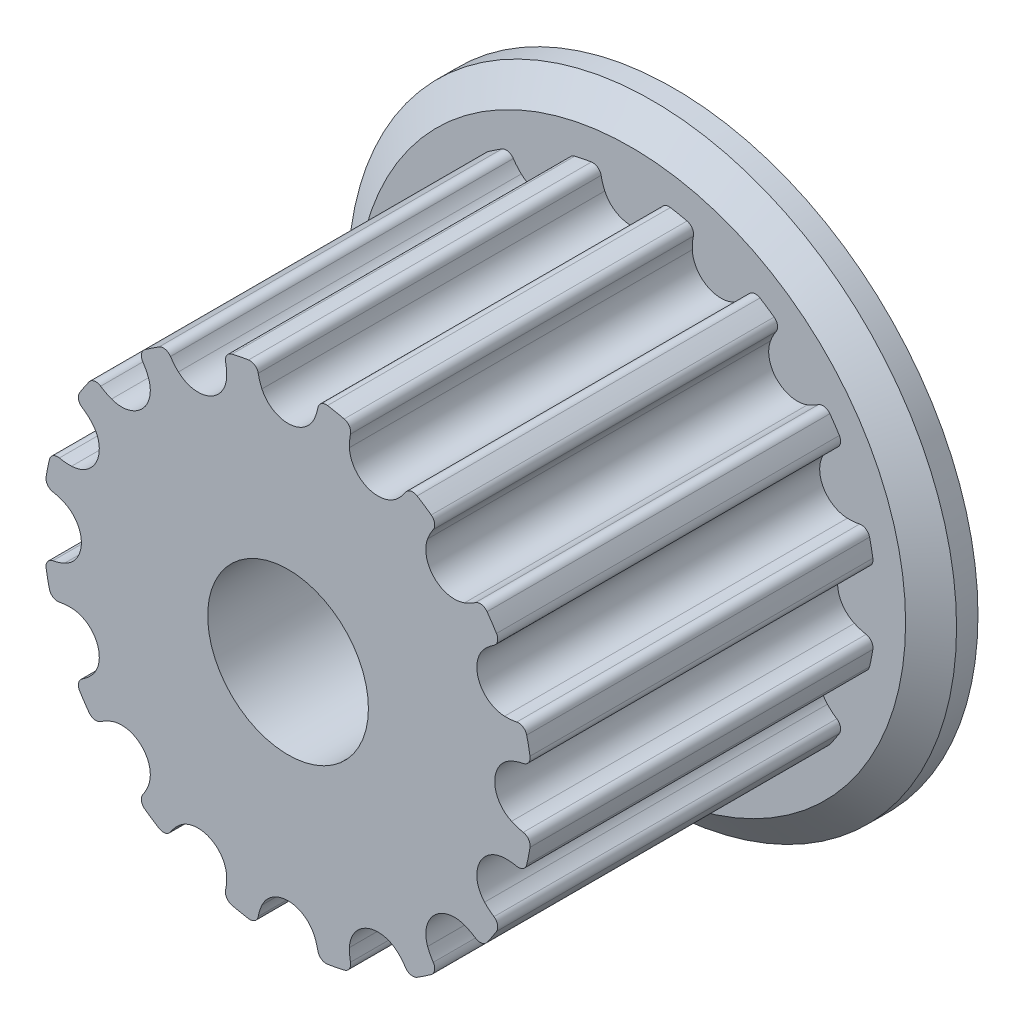
SolidWorks part; units mm, degrees
ref_plane "Front Plane" through (0, 0, 0) normal (0, 0, 1) x (1, 0, 0)
ref_plane "Top Plane" through (0, 0, 0) normal (0, 1, 0) x (1, 0, 0)
ref_plane "Right Plane" through (0, 0, 0) normal (1, 0, 0) x (0, 0, -1)
sketch "Sketch1" plane through (0, 0, 0) normal (0, 0, 1) x (1, 0, 0)
  line L1 (-2.553, 6.1245) -> (2.553, 6.1245) construction
  line L4 (0, 0) -> (0, 6.1245) construction
  line L5 (0, 6.1245) -> (0, 12.0714) construction
  line L6 (0, 7.6455) -> (2.9417, 7.0569) construction
  line L7 (2.9417, 7.0569) -> (3.8741, 6.6682) construction
  line L8 (2.9417, 7.0569) -> (2.553, 6.1245) construction
  line L9 (-2.9417, 7.0569) -> (-2.553, 6.1245) construction
  line L10 (-2.7951, 6.7052) -> (-3.7579, 9.015)
  line L11 (-3.7579, 9.015) -> (3.7579, 9.015)
  line L12 (3.7579, 9.015) -> (2.7951, 6.7052)
  circle A0 centre (0, 0) radius 7.6455 construction
  circle A1 centre (0, 0) radius 9.015 construction
  circle A2 centre (0, 0) radius 7.2645 construction
  arc A3 (-0.7739, 6.6229) -> (0.7739, 6.6229) centre (0, 6.9745) ccw
  arc A4 (-0.7739, 6.6229) -> (-0.8836, 6.9694) centre (0.61, 7.2516) cw
  arc A5 (-2.7951, 6.7052) -> (-1.1695, 7.1697) centre (0, 0) cw
  arc A6 (-0.8836, 6.9694) -> (-1.1695, 7.1697) centre (-1.1292, 6.923) ccw
  arc A7 (2.7951, 6.7052) -> (1.1695, 7.1697) centre (0, 0) ccw
  arc A8 (0.8836, 6.9694) -> (1.1695, 7.1697) centre (1.1292, 6.923) cw
  arc A9 (0.7739, 6.6229) -> (0.8836, 6.9694) centre (-0.61, 7.2516) ccw
  point P6 (0, 20.9083)
  point P11 (0, 7.6455)
  point P13 (0, 9.015)
  point P14 (0, 7.2645)
  dimension "D1" = 8.8369
  dimension "D2" = 4.4259
sketch "Sketch2" plane through (0, 0, 0) normal (1, 0, 0) x (0, 0, -1)
  line L0 (-8.775, 2.3812) -> (8.775, 2.3812)
  line L1 (-8.775, 2.3812) -> (-8.775, 9.015)
  line L2 (-3.29, 9.015) -> (-8.775, 9.015)
  line L3 (-3.925, 2.3813) -> (-3.925, 9.015) construction
  line L4 (-3.925, 9.015) -> (-2.655, 9.015) construction
  line L5 (-2.655, 9.015) -> (-2.655, 7.2645) construction
  line L6 (-2.655, 7.2645) -> (7.505, 7.2645)
  line L7 (7.505, 7.2645) -> (7.505, 9.015) construction
  line L8 (7.505, 9.015) -> (8.775, 9.015) construction
  line L9 (8.775, 9.015) -> (8.775, 2.3812)
  line L10 (-8.775, 0) -> (8.775, 0) construction
  line L11 (8.14, 9.015) -> (7.505, 8.1398)
  line L12 (-2.655, 8.1398) -> (-3.29, 9.015)
  line L14 (-2.655, 8.1398) -> (-2.655, 7.2645)
  line L15 (7.505, 7.2645) -> (7.505, 8.1398)
  line L16 (8.14, 9.015) -> (8.775, 9.015)
  arc A0 (-2.655, 8.1398) -> (-3.29, 9.015) centre (-3.5757, 8.1398) ccw construction
  arc A1 (7.505, 8.1398) -> (8.14, 9.015) centre (8.4257, 8.1398) cw construction
  point P12 (-2.655, 8.1398)
  point P14 (-3.29, 9.015)
  point P20 (7.505, 8.1398)
  point P21 (8.14, 9.015)
  point P25 (7.505, 0)
  point P26 (-2.655, 0)
  dimension "OA" = 17.55
  dimension "Bore" = 4.7625
  dimension "Outside Width" = 11.43
  dimension "Inside Width" = 10.16
revolve "Revolve1" add sketch "Sketch2" angle 360 mid plane about L10
sketch "Sketch3" plane through (0, 0, 0) normal (0, 0, 1) x (1, 0, 0)
  line L6 (3.7579, 9.015) -> (-3.7579, 9.015)
  line L7 (2.7951, 6.7052) -> (3.7579, 9.015)
  line L8 (-3.7579, 9.015) -> (-2.7951, 6.7052)
  line L9 (3.7579, 9.015) -> (-3.7579, 9.015)
  line L10 (2.7951, 6.7052) -> (3.7579, 9.015)
  line L11 (-3.7579, 9.015) -> (-2.7951, 6.7052)
  arc A8 (2.7951, 6.7052) -> (1.1695, 7.1697) centre (0, 0) ccw
  arc A9 (1.1695, 7.1697) -> (0.8836, 6.9694) centre (1.1292, 6.923) ccw
  arc A10 (0.7739, 6.6229) -> (0.8836, 6.9694) centre (-0.61, 7.2516) ccw
  arc A11 (-0.7739, 6.6229) -> (0.7739, 6.6229) centre (0, 6.9745) ccw
  arc A12 (-0.8836, 6.9694) -> (-0.7739, 6.6229) centre (0.61, 7.2516) ccw
  arc A13 (-0.8836, 6.9694) -> (-1.1695, 7.1697) centre (-1.1292, 6.923) ccw
  arc A14 (-1.1695, 7.1697) -> (-2.7951, 6.7052) centre (0, 0) ccw
  arc A15 (2.7951, 6.7052) -> (1.1695, 7.1697) centre (0, 0) ccw
  arc A16 (1.1695, 7.1697) -> (0.8836, 6.9694) centre (1.1292, 6.923) ccw
  arc A17 (0.7739, 6.6229) -> (0.8836, 6.9694) centre (-0.61, 7.2516) ccw
  arc A18 (-0.7739, 6.6229) -> (0.7739, 6.6229) centre (0, 6.9745) ccw
  arc A19 (-0.8836, 6.9694) -> (-0.7739, 6.6229) centre (0.61, 7.2516) ccw
  arc A20 (-0.8836, 6.9694) -> (-1.1695, 7.1697) centre (-1.1292, 6.923) ccw
  arc A21 (-1.1695, 7.1697) -> (-2.7951, 6.7052) centre (0, 0) ccw
  dimension "D1" = 0
extrude "Cut-Extrude1" cut sketch "Sketch3" against normal up to vertex (7.505 mm away) from vertex up to point (0, 7.2645, -7.505) starting at point (0, 7.2645, 2.655)
pattern_circular "CirPattern1" count 16 over 360 about axis through (0, 0, 8.775) along (0, 0, 1) of "Cut-Extrude1"
sketch "Sketch4" plane through (0, 0, 0) normal (1, 0, 0) x (0, -1, 0)
  line L0 (0, -2.655) -> (0, -8.775) construction
  line L1 (-2.3812, -8.775) -> (2.3812, -8.775) construction
  line L2 (8.1398, -2.655) -> (-8.1398, -2.655) construction
  circle A0 centre (0, -5.715) radius 1.7526
extrude "Cut-Extrude2" cut sketch "Sketch4" along normal through all
ref_plane "Plane1" through (0, 0, 5.715) normal (0, 0, 1) x (1, 0, 0)
sketch "Sketch5" plane through (0, 0, 5.715) normal (0, 0, 1) x (1, 0, 0)
  line L0 (0, 0) -> (0, 9.015) construction
  line L1 (2.3812, -1.3716) -> (2.3812, 0)
  line L2 (2.7622, -1.7526) -> (8.462, -1.7526)
  line L3 (2.3812, 0) -> (9.015, 0) construction
  line L4 (2.3812, 0) -> (8.843, 0)
  line L5 (8.843, 0) -> (8.843, -1.3716)
  line L6 (2.7622, -1.7526) -> (2.3812, -1.3716)
  line L7 (8.843, -1.3716) -> (8.462, -1.7526)
  circle A0 centre (0, 0) radius 9.015 construction
  circle A1 centre (0, 0) radius 2.3812 construction
  point P2 (2.3812, -1.7526)
  point P11 (8.843, -1.7526)
revolve "Revolve2" add sketch "Sketch5" angle 360 mid plane about L4
sketch "Sketch6" plane through (8.843, 5.3841, 0) normal (-1, 0, 0) x (0, -1, 0)
  line L1 (5.3841, 6.7269) -> (4.5078, 6.2209)
  line L2 (4.5078, 6.2209) -> (4.5078, 5.2091)
  line L3 (4.5078, 5.2091) -> (5.3841, 4.7031)
  line L4 (5.3841, 4.7031) -> (6.2604, 5.2091)
  line L5 (6.2604, 5.2091) -> (6.2604, 6.2209)
  line L6 (6.2604, 6.2209) -> (5.3841, 6.7269)
  circle A0 centre (5.3841, 5.715) radius 0.8763 construction
  dimension "D1" = 1.7526
extrude "Cut-Extrude3" cut sketch "Sketch6" along normal blind 1.3144
pattern_circular "CirPattern3" count 2 over 90 about axis through (0, 0, 8.775) along (0, 0, 1) of "Cut-Extrude2", "Revolve2", "Cut-Extrude3"
chamfer "Chamfer1" distance 0.2807 angle 45 2 edges at (2.3812, 0, 8.775) (9.015, 0, 8.775)
ref_axis "Center Axis 1" through (0, 0, -8.775) along (0, 0, 1)
ref_plane "Contact Plane 1" through (0, 0, 8.775) normal (0, 0, 1) x (1, 0, 0)
ref_plane "Contact Plane 2" through (0, 0, -8.775) normal (0, 0, -1) x (-1, 0, 0)
sketch "Sketch7" plane through (0, 0, 8.775) normal (0, 0, 1) x (1, 0, 0)
  circle A0 centre (0, 0) radius 9.015 construction
  circle A1 centre (0, 0) radius 9.015
extrude "Cut-Extrude4" cut sketch "Sketch7" against normal up to surface (6.12 mm away) up to face at (0, 0, 2.655)
equation "\"D2@Sketch1\"= \"D1@Sketch1\" / 2"
equation "\"D1@Sketch6\" = \"Set Screw@Sketch4\" / 2"
equation "\"D1@Cut-Extrude3\" = \"D1@Sketch6\"*.75"
